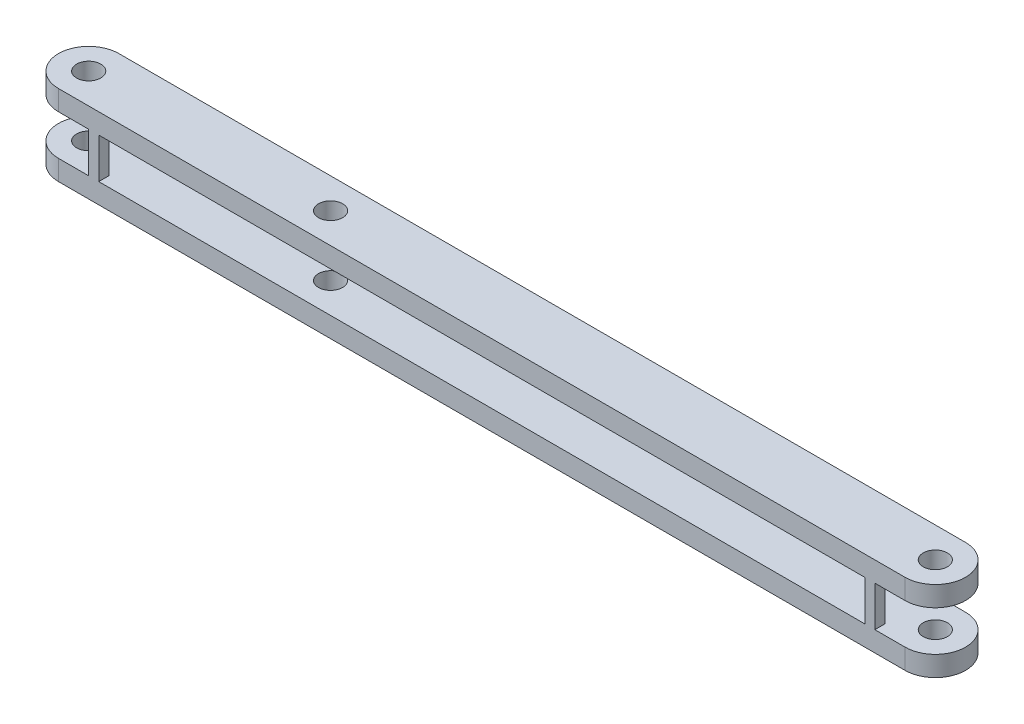
SolidWorks part; units mm, degrees
ref_plane "前视基准面" through (0, 0, 0) normal (0, 0, 1) x (1, 0, 0)
ref_plane "上视基准面" through (0, 0, 0) normal (0, 1, 0) x (1, 0, 0)
ref_plane "右视基准面" through (0, 0, 0) normal (1, 0, 0) x (0, 0, -1)
sketch "草图1" plane through (0, 0, 0) normal (0, 1, 0) x (1, 0, 0)
  line L0 (-105, 0) -> (105, 0) construction
  line L1 (-105, 7.5) -> (105, 7.5)
  line L2 (-105, -7.5) -> (105, -7.5)
  arc A0 (-105, 7.5) -> (-105, -7.5) centre (-105, 0) ccw
  arc A1 (105, -7.5) -> (105, 7.5) centre (105, 0) ccw
  point P3 (0, 0)
  dimension "D1" = 210
  dimension "D2" = 15
extrude "凸台-拉伸1" add sketch "草图1" along normal blind 20
sketch "草图2" plane through (0, 0, -7.5) normal (0, 0, -1) x (-1, 0, 0)
  line L0 (0, 0) -> (0, 10) construction
  line L1 (95, 5) -> (-95, 5)
  line L2 (95, 5) -> (95, 15)
  line L3 (95, 15) -> (-95, 15)
  line L4 (-95, 5) -> (-95, 15)
  line L5 (95, 5) -> (-95, 15) construction
  line L6 (95, 15) -> (-95, 5) construction
  line L7 (-105, 0) -> (105, 0) construction
  point P0 (0, 10)
  dimension "D1" = 10
  dimension "D2" = 10
  dimension "D3" = 190
extrude "切除-拉伸3" cut sketch "草图2" against normal through all
sketch "草图3" plane through (0, 0, -7.5) normal (0, 0, -1) x (-1, 0, 0)
  line L0 (-95, 5) -> (95, 5) construction
  line L1 (112.5, 15) -> (97.5, 15)
  line L2 (112.5, 15) -> (112.5, 5)
  line L3 (112.5, 5) -> (97.5, 5)
  line L4 (97.5, 15) -> (97.5, 5)
  line L5 (95, 15) -> (-95, 15) construction
  line L6 (112.5, 0) -> (112.5, 20) construction
  line L7 (0, 0) -> (0, 43.872) construction
  line L8 (-105, 0) -> (105, 0) construction
  line L9 (-97.5, 15) -> (-97.5, 5)
  line L10 (-112.5, 5) -> (-97.5, 5)
  line L11 (-112.5, 15) -> (-112.5, 5)
  line L12 (-112.5, 15) -> (-97.5, 15)
  dimension "D1" = 15
extrude "切除-拉伸4" cut sketch "草图3" against normal through all
sketch "草图4" plane through (-97.5, 0, 0) normal (-1, 0, 0) x (0, 0, 1)
  line L0 (7.5, 5) -> (-7.5, 5) construction
  line L1 (5, 15) -> (-5, 15)
  line L2 (5, 15) -> (5, 5)
  line L3 (5, 5) -> (-5, 5)
  line L4 (-5, 15) -> (-5, 5)
  line L5 (5, 15) -> (-5, 5) construction
  line L6 (5, 5) -> (-5, 15) construction
  line L7 (0, 0) -> (0, 10) construction
  line L8 (7.5, 15) -> (-7.5, 15) construction
  point P0 (0, 10)
  dimension "D1" = 10
extrude "切除-拉伸5" cut sketch "草图4" against normal through all
sketch "草图5" plane through (0, 20, 0) normal (0, 1, 0) x (1, 0, 0)
  line L0 (-105, 0) -> (0, 0) construction
  line L1 (0, 0) -> (105, 0) construction
  circle A0 centre (-105, 0) radius 3
  circle A1 centre (105, 0) radius 3
  dimension "D1" = 6
  dimension "D2" = 6
  dimension "D3" = 105
  dimension "D4" = 105
extrude "切除-拉伸6" cut sketch "草图5" against normal through all
sketch "草图6" plane through (0, 20, 0) normal (0, 1, 0) x (1, 0, 0)
  line L0 (-45, 0) -> (0, 0) construction
  circle A0 centre (-45, 0) radius 3
  circle A1 centre (-105, 0) radius 4 construction
  dimension "D2" = 6
  dimension "D1" = 60
extrude "切除-拉伸7" cut sketch "草图6" against normal through all
